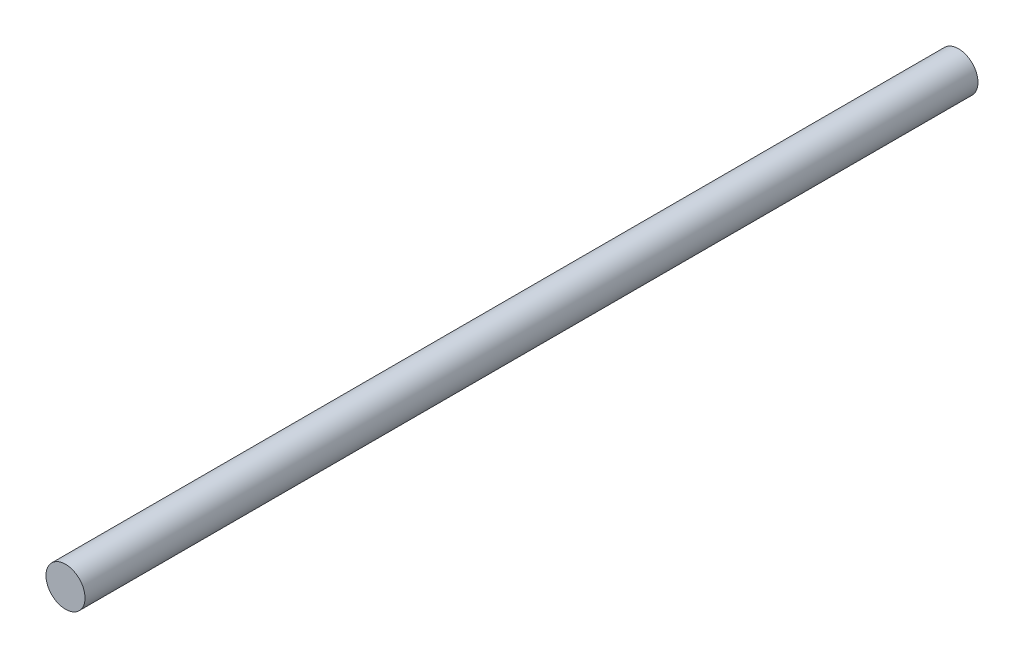
SolidWorks part; units mm, degrees
material "1060 Alloy"
ref_plane "Front Plane" through (0, 0, 0) normal (0, 0, 1) x (1, 0, 0)
ref_plane "Top Plane" through (0, 0, 0) normal (0, 1, 0) x (1, 0, 0)
ref_plane "Right Plane" through (0, 0, 0) normal (1, 0, 0) x (0, 0, -1)
sketch "Sketch1" plane through (0, 0, 0) normal (0, 0, 1) x (1, 0, 0)
  circle A0 centre (0, 0) radius 5
  dimension "D1" = 10
extrude "Boss-Extrude1" add sketch "Sketch1" along normal blind 228.6
